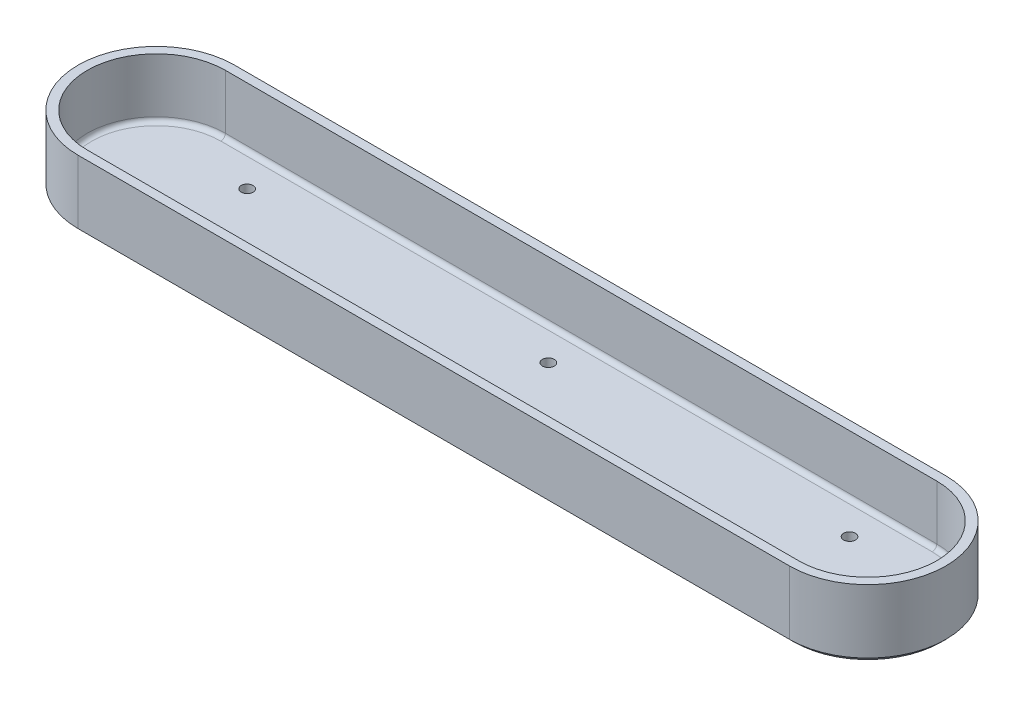
SolidWorks part; units mm, degrees
material "PLA"
ref_plane "Front Plane" through (0, 0, 0) normal (0, 0, 1) x (1, 0, 0)
ref_plane "Top Plane" through (0, 0, 0) normal (0, 1, 0) x (1, 0, 0)
ref_plane "Right Plane" through (0, 0, 0) normal (1, 0, 0) x (0, 0, -1)
sketch "Sketch1" plane through (0, 0, 0) normal (0, 1, 0) x (1, 0, 0)
  line L0 (-99.441, 0) -> (99.441, 0) construction
  line L1 (0, -55.9739) -> (0, 55.9739) construction
  line L2 (-99.441, 19.304) -> (99.441, 19.304)
  line L3 (-99.441, -19.304) -> (99.441, -19.304)
  arc A0 (-99.441, 19.304) -> (-99.441, -19.304) centre (-99.441, 0) ccw
  arc A1 (99.441, 19.304) -> (99.441, -19.304) centre (99.441, 0) cw
  circle A2 centre (-99.441, 0) radius 19.05 construction
  point P4 (0, 0)
  point P10 (0, 0)
  dimension "D2" = 0.254
  dimension "D3" = 38.1
  dimension "D1" = 198.882
extrude "MainBlock" add sketch "Sketch1" along normal blind 2.54
sketch "Sketch2" plane through (0, 0, 0) normal (0, -1, 0) x (1, 0, 0)
  line L0 (0, 0) -> (0, 50000) construction
  line L1 (-99.441, 21.844) -> (99.441, 21.844)
  line L2 (-99.441, -19.304) -> (99.441, -19.304)
  line L3 (99.441, 19.304) -> (-99.441, 19.304)
  line L5 (99.441, 19.304) -> (-99.441, 19.304)
  line L6 (-95.25, 0) -> (49904.75, 0) construction
  line L7 (99.441, -19.304) -> (-99.441, -19.304)
  line L8 (-99.441, -21.844) -> (99.441, -21.844)
  arc A0 (-99.441, 21.844) -> (-99.441, -21.844) centre (-99.441, 0) ccw
  arc A1 (99.441, 19.304) -> (99.441, -19.304) centre (99.441, 0) cw
  arc A2 (-99.441, 19.304) -> (-99.441, -19.304) centre (-99.441, 0) ccw
  arc A3 (99.441, -19.304) -> (99.441, 19.304) centre (99.441, 0) ccw
  arc A4 (-99.441, 19.304) -> (-99.441, -19.304) centre (-99.441, 0) ccw
  arc A6 (99.441, 21.844) -> (99.441, -21.844) centre (99.441, 0) cw
  point P0 (0, 19.304)
  point P15 (0, 21.844)
  point P16 (0, -19.304)
  point P19 (0, -21.844)
  dimension "D2" = 2.54
  dimension "2.1" = 43.688
  dimension "D1" = 0
extrude "Boss-Extrude1" add sketch "Sketch2" against normal blind 19.05
sketch "Sketch3" plane through (0, 0, 0) normal (0, -1, 0) x (1, 0, 0)
  line L0 (0, 0) -> (50000, 0) construction
  line L1 (0, 0) -> (0, 50000) construction
  line L2 (-99.441, 0.9216) -> (-99.441, 50000.9216) construction
  arc A0 (-99.441, 21.844) -> (-99.441, -21.844) centre (-99.441, 0) ccw construction
  arc A1 (-99.441, 21.844) -> (-99.441, -21.844) centre (-99.441, 0) ccw construction
  circle A2 centre (0, 10.16) radius 1.651
  circle A3 centre (-84.201, 10.16) radius 1.651
  circle A4 centre (84.201, 10.16) radius 1.651
  circle A5 centre (84.201, -10.16) radius 1.651
  circle A6 centre (-84.201, -10.16) radius 1.651
  circle A7 centre (0, -10.16) radius 1.651
  dimension "D1" = 3.302
  dimension "D4" = 3.302
  dimension "D2" = 10.16
  dimension "D3" = 10.16
  dimension "D5" = 15.24
extrude "Mount-Holes" cut sketch "Sketch3" against normal through all
fillet "Fillet1" radius 1.27 4 edges at (118.745, 2.54, 0) (0, 2.54, 19.304) (-118.745, 2.54, 0) (0, 2.54, -19.304)
chamfer "Chamfer1" distance 1.27 angle 45 4 edges at (0, 0, 21.844) (-121.285, 0, 0) (121.285, 0, 0) (0, 0, -21.844)
equation "\"D4@Sketch3\"=\"D1@Sketch3\""
